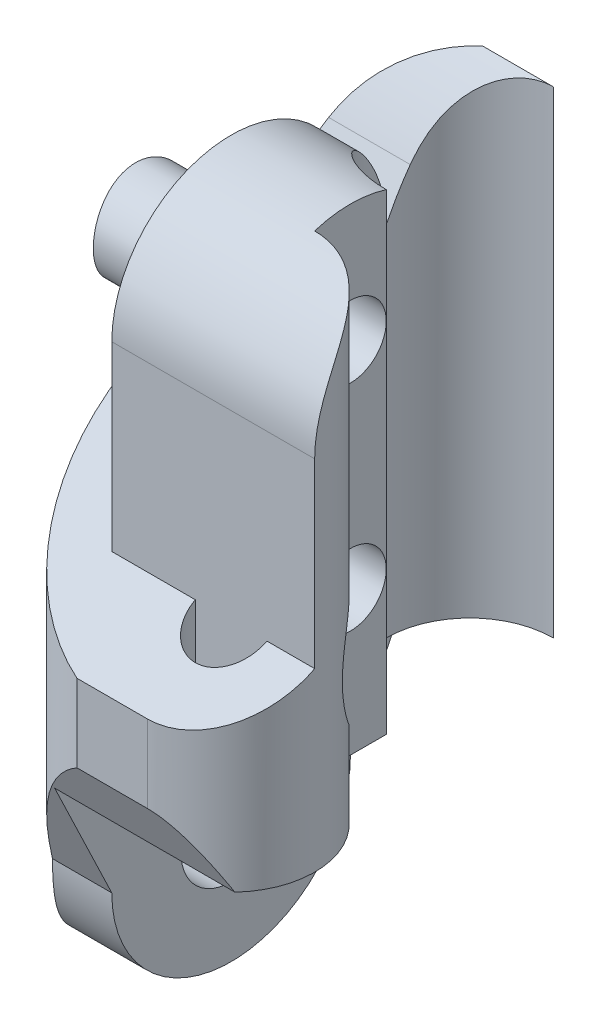
SolidWorks part; units mm, degrees
ref_plane "Front Plane" through (0, 0, 0) normal (0, 0, 1) x (1, 0, 0)
ref_plane "Top Plane" through (0, 0, 0) normal (0, 1, 0) x (1, 0, 0)
ref_plane "Right Plane" through (0, 0, 0) normal (1, 0, 0) x (0, 0, -1)
sketch "Sketch1" plane through (0, 0, 0) normal (0, 1, 0) x (1, 0, 0)
  line L0 (-2.958, 8.5) -> (2.958, 8.5)
  line L1 (-2.958, -8.5) -> (2.958, -8.5)
  arc A0 (-2.958, 8.5) -> (-2.958, -8.5) centre (0, 0) ccw
  arc A1 (2.958, 8.5) -> (2.958, -8.5) centre (0, 0) cw
  point P9 (-9, 0)
  point P10 (9, 0)
  dimension "D1" = 18
  dimension "D2" = 17
extrude "Boss-Extrude1" add sketch "Sketch1" along normal blind 30
sketch "Sketch2" plane through (0, 0, 0) normal (0, -1, 0) x (1, 0, 0)
  line L0 (1.5, 5) -> (-1.5, 5)
  line L1 (1.5, -5) -> (-1.5, -5)
  line L2 (0, -5) -> (0, 5) construction
  arc A2 (-1.5, 5) -> (1.5, 5) centre (0, 5) cw
  arc A3 (-1.5, -5) -> (1.5, -5) centre (0, -5) ccw
  dimension "D1" = 1.5
  dimension "D2" = 10
extrude "Cut-Extrude1" cut sketch "Sketch2" against normal blind 35
sketch "Sketch3" plane through (0, 0, -8.5) normal (0, 0, -1) x (-1, 0, 0)
  line L0 (5, 0) -> (5, 10)
  line L1 (5, 10) -> (-5, 10)
  line L2 (-5, 10) -> (-5, 0)
  line L3 (5, 0) -> (-5, 0)
  line L4 (-2.958, 0) -> (2.958, 0) construction
  point P10 (0, 0)
  dimension "D1" = 10
  dimension "D2" = 10
extrude "Cut-Extrude2" cut sketch "Sketch3" against normal up to surface (17 mm away) up to face at (0, 15, 8.5)
sketch "Sketch4" plane through (5, 0, 0) normal (-1, 0, 0) x (0, 0, 1)
  line L0 (-7.4833, 10) -> (-5, 5)
  line L1 (8.5, 12.3086) -> (5, 5)
  line L2 (7.4833, 0) -> (-7.4833, 0) construction
  line L3 (-7.4833, 10) -> (-9.8579, -1.8222)
  line L4 (-9.8579, -1.8222) -> (9.8579, -1.8222)
  line L6 (8.5, 30) -> (8.5, 10) construction
  line L7 (9.8579, -1.8222) -> (8.5, 12.3086)
  arc A0 (-5, 5) -> (5, 5) centre (0, 5) ccw
  circle A1 centre (0, 5) radius 2.1
  point P7 (0, 0)
  dimension "D1" = 4.2
  dimension "D2" = 5
  dimension "D3" = 12.0584
  dimension "D4" = 37.769
extrude "Cut-Extrude3" cut sketch "Sketch4" against normal mid plane 35
ref_plane "Plane1" through (-2.958, 0, 0) normal (-1, 0, 0) x (0, 0, 1)
sketch "Sketch6" plane through (-2.958, 0, 0) normal (-1, 0, 0) x (0, 0, 1)
  line L0 (8.5, 15.5583) -> (0, 20)
  line L1 (8.5, 30) -> (8.5, 12.3086) construction
  line L2 (-5, 25) -> (-5.8896, 26.7912)
  line L3 (8.5, 30) -> (-8.5, 30) construction
  line L4 (8.5, 15.5583) -> (17.803, 42.886)
  line L6 (-7.4833, 10) -> (-5, 5) construction
  line L7 (-8.5, 30) -> (17.803, 42.886)
  line L8 (5, 5) -> (8.5, 12.3086) construction
  arc A0 (0, 20) -> (-5, 25) centre (0, 25) cw
  circle A1 centre (0, 25) radius 2
  arc A2 (-5.8896, 26.7912) -> (-8.5, 30) centre (-14.3043, 22.612) ccw
  point P10 (0, 20)
  dimension "D1" = 5
  dimension "D3" = 4
  dimension "D2" = 5
  dimension "D4" = 8.5
  dimension "D5" = 2
  dimension "D6" = 92
extrude "Cut-Extrude5" cut sketch "Sketch6" against normal blind 9.6 from surface starting at face at (5, 7.1, 0)
sketch "Sketch7" plane through (5, 0, 0) normal (1, 0, 0) x (0, 0, -1)
  line L0 (5, 25) -> (5.8896, 26.7912)
  line L2 (-11.8561, 46.3446) -> (-15.7899, 32.06)
  line L3 (-7.4833, 30) -> (7.4833, 30) construction
  line L4 (-5, 25) -> (-5, 17.3872)
  line L5 (-7.4833, 16.0896) -> (0, 20) construction
  line L6 (-5, 17.3872) -> (-10.7623, 14.3761)
  line L7 (-10.7623, 14.3761) -> (-15.7899, 32.06)
  line L8 (5.8896, 26.7912) -> (5, 25) construction
  line L9 (8.5, 30) -> (-11.8561, 46.3446)
  line L10 (-8.5, 12.3086) -> (-5, 5) construction
  arc A0 (5, 25) -> (-5, 25) centre (0, 25) ccw
  arc A1 (5.8896, 26.7912) -> (8.5, 30) centre (14.3043, 22.612) cw
  arc A2 (7.4833, 29.0732) -> (5.8896, 26.7912) centre (14.3043, 22.612) ccw construction
  dimension "D1" = 5
  dimension "D2" = 92
fillet "Fillet3" radius 1 4 edges at (0, 10, 6.5) (0, 10, 5) (0, 10, -6.5) (0, 10, -5)
extrude "Cut-Extrude6" cut sketch "Sketch6<3>" along normal blind 6.604 from surface starting at face at (-5, 2.9, 0)
sketch "Sketch6<3>" plane through (-2.958, 0, 0) normal (-1, 0, 0) x (0, 0, 1) same geometry as "Sketch6"
extrude "Cut-Extrude7" cut sketch "Sketch7" against normal blind 14.986
sketch "Sketch8" plane through (0, 10, 0) normal (0, -1, 0) x (1, 0, 0)
  line L0 (0, 1.5) -> (0, -1.5)
  line L1 (-2.958, -8.5) -> (2.958, -8.5) construction
  line L2 (2.958, 8.5) -> (-2.958, 8.5) construction
  line L3 (0, 8.5) -> (-4.7901, 15.219)
  line L4 (-4.7901, 15.219) -> (34.9648, -1.5)
  line L5 (34.9648, -1.5) -> (-4.7901, -16.0136)
  line L6 (-4.7901, -16.0136) -> (0, -8.5)
  arc A0 (0, -1.5) -> (0, -8.5) centre (0, -5) ccw
  arc A1 (0, 1.5) -> (0, 8.5) centre (0, 5) ccw
  arc A4 (2.2913, 4) -> (0.7187, 7.3945) centre (0, 5) ccw construction
  arc A5 (-2.2913, -4) -> (2.2913, -4) centre (0, -5) ccw construction
extrude "Cut-Extrude8" cut sketch "Sketch8" against normal mid plane 62.992
sketch "Sketch9" plane through (0, 0, 0) normal (1, 0, 0) x (0, 0, -1)
  line L1 (1.5, 10) -> (-1.5, 10) construction
  circle A0 centre (0, 16) radius 1.5
  dimension "D2" = 3
  dimension "D1" = 6
extrude "Cut-Extrude9" cut sketch "Sketch9" against normal blind 14.224
sketch "Sketch13" plane through (0, 0, 0) normal (1, 0, 0) x (0, 0, -1)
  line L1 (1.5, 29.7697) -> (1.5, 16) construction
  circle A0 centre (0, 25) radius 1.5
  circle A2 centre (0, 25) radius 2 construction
sketch "Sketch14" plane through (0, 0, 0) normal (1, 0, 0) x (0, 0, -1)
  line L0 (0, 12.5) -> (0, 19.5)
  arc A0 (0, 19.5) -> (0, 12.5) centre (0, 16) ccw
  arc A1 (-1.5, 16) -> (1.5, 16) centre (0, 16) ccw construction
  dimension "D1" = 3.5
extrude "Cut-Extrude11" cut sketch "Sketch14" along normal blind 6.048
extrude "Cut-Extrude12" cut sketch "Sketch13" against normal blind 3
sketch "Sketch15" plane through (0, 0, 0) normal (1, 0, 0) x (0, 0, -1)
  circle A0 centre (0, 16) radius 2.75
  dimension "D1" = 5.5
extrude "Cut-Extrude13" cut sketch "Sketch15" against normal blind 7.572 from offset 5.5 offset against normal yes
